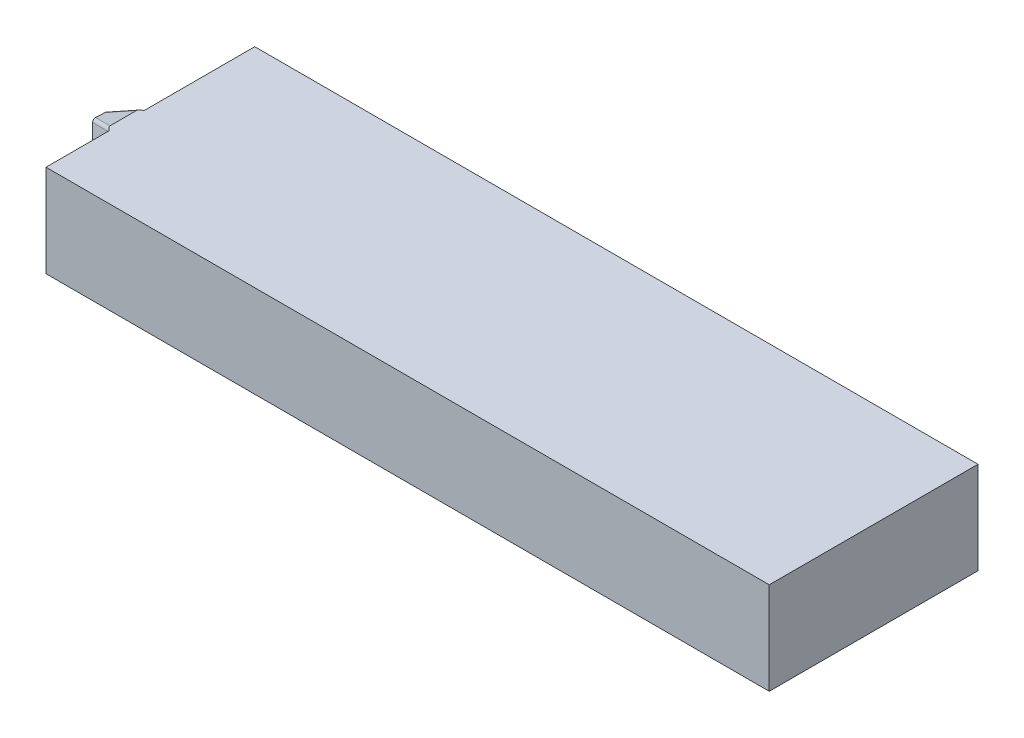
SolidWorks part; units mm, degrees
material "A-2 Steel"
ref_plane "Alzado" through (0, 0, 0) normal (0, 0, 1) x (1, 0, 0)
ref_plane "Planta" through (0, 0, 0) normal (0, 1, 0) x (1, 0, 0)
ref_plane "Vista lateral" through (0, 0, 0) normal (1, 0, 0) x (0, 0, -1)
sketch "Croquis1" plane through (0, 0, 0) normal (0, 1, 0) x (1, 0, 0)
  line L1 (11, 3.175) -> (-11, 3.175)
  line L2 (11, 3.175) -> (11, -3.175)
  line L3 (11, -3.175) -> (-11, -3.175)
  line L4 (-11, 3.175) -> (-11, -3.175)
  line L5 (0, -3.175) -> (0, 3.175) construction
  line L6 (11, 0) -> (-11, 0) construction
  point P124 (0, 0)
  dimension "D1" = 6.35
  dimension "D2" = 22
extrude "Saliente-Extruir1" add sketch "Croquis1" along normal blind 2.8067
sketch "Croquis2" plane through (-11, 0, 0) normal (-1, 0, 0) x (0, 0, 1)
  line L0 (1.5, 2.8067) -> (1.5, 0) construction
  line L1 (-3.175, 2.8067) -> (3.175, 2.8067) construction
  line L2 (-3.175, 0) -> (3.175, 0) construction
  line L3 (-1.5, 2.8067) -> (-1.5, 0) construction
  line L4 (-1.5, 1.4034) -> (1.5, 1.4034) construction
  line L5 (0, 0) -> (0, 1.4034) construction
  text T0 "4" font "Arial" height 3.0226
  dimension "D1" = 3
extrude "Saliente-Extruir2" add sketch "Croquis2" along normal blind 1.077 draft 8
chamfer "Chaflán1" distance 1.0922 angle 18 11 edges at (-11, 1.2871, 1.19) (-11, 1.8877, 0.88) (-11, 2.4884, 0.629) (-11, 1.8493, -0.5529) (-11, 0.958, -1.4838) (-11, 0.7058, -0.5538) (-11, 0.5121, 0.3762) (-11, 0.3183, 0.6281) (-11, 0.5121, 0.88) (-11, 0.7058, 1.19) (-11, 0.9965, 1.5) first distance on face at (-11.5385, 1.2114, 1.1143) first distance on face at (-11.5385, 1.8121, 0.8043) first distance on face at (-11.5385, 2.4127, 0.6029) first distance on face at (-11.5385, 1.7915, -0.5033) first distance on face at (-11.5385, 0.9759, -1.4082) first distance on face at (-11.5385, 0.7815, -0.4781) first distance on face at (-11.5385, 0.5877, 0.4519) first distance on face at (-11.5385, 0.394, 0.6281) first distance on face at (-11.5385, 0.5877, 0.8043) first distance on face at (-11.5385, 0.7815, 1.1143) first distance on face at (-11.5385, 0.9965, 1.4243)
chamfer "Chaflán2" distance 1.0922 angle 8 3 edges at (-11, 1.6328, 0.3762) (-11, 1.2871, -0.1269) (-11, 1.6328, -0.1269) first distance on face at (-11.5385, 1.6669, 0.4519) first distance on face at (-11.5385, 1.2114, -0.211) first distance on face at (-11.5385, 1.6669, -0.211)
fillet "Redondeo1" radius 0.0992 14 edges at (-11.5385, 1.2908, -0.6181) (-11.5385, 1.2908, 0.3725) (-11.5385, 1.9715, 0.3725) (-11.5971, 2.5727, 0.3519) (-11.5971, 2.5727, 0.9643) (-11.5385, 1.4, 0.9929) (-11.5385, 1.4, 1.6129) (-11.5385, 0.5929, 1.6129) (-11.5385, 0.5929, 0.9929) (-11.5971, 0.234, 0.9643) (-11.5971, 0.234, 0.2919) (-11.5385, 0.5929, 0.2633) (-11.5385, 0.5929, -1.5967) (-11.5385, 1.2696, -1.5967)
sketch "Croquis3" plane through (0, 0, 0) normal (0, -1, 0) x (1, 0, 0)
  line L0 (-12.077, -1.3341) -> (-12.077, 1.3502)
  arc A0 (-12.077, -1.3341) -> (-12.077, 1.3502) centre (-18.2835, 0.0081) ccw
  dimension "D1" = 6.35
extrude "Cortar-Extruir1" cut sketch "Croquis3" against normal through all
